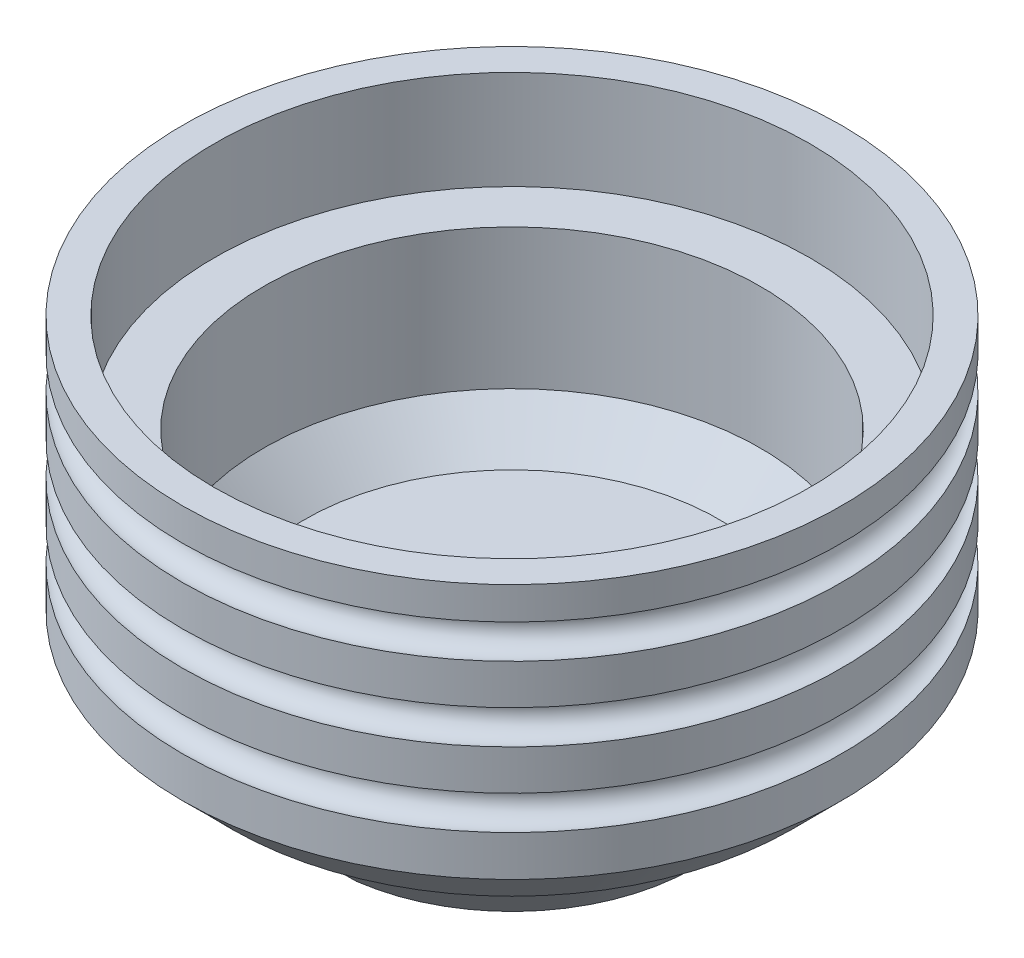
SolidWorks part; units mm, degrees
material "ABS PC"
ref_plane "正面" through (0, 0, 0) normal (0, 0, 1) x (1, 0, 0)
ref_plane "平面" through (0, 0, 0) normal (0, 1, 0) x (1, 0, 0)
ref_plane "右側面" through (0, 0, 0) normal (1, 0, 0) x (0, 0, -1)
sketch "ｽｹｯﾁ2" plane through (0, 0, 0) normal (1, 0, 0) x (0, 0, -1)
  line L0 (4, -2) -> (4, -27.3) construction
  line L1 (-1.125, -19) -> (-1.125, -6)
  line L2 (-1.125, -6) -> (-26.15, -6)
  line L3 (-26.15, -6) -> (-26.15, 16)
  line L4 (-26.15, 16) -> (-32.15, 16)
  line L5 (-32.15, 16) -> (-32.15, 28)
  line L6 (-32.15, 28) -> (-36, 28)
  line L7 (-36, 28) -> (-36, -9)
  line L14 (-36, -9) -> (-16.125, -9)
  line L16 (-1, -2) -> (9, -2) construction
  line L17 (-9.15, -3) -> (17.15, -3) construction
  line L19 (-1.125, -19) -> (-16.125, -19)
  line L20 (-16.125, -19) -> (-16.125, -9)
  line L21 (-35.5, 13) -> (-26.15, 13) construction
  line L22 (-35.5, 28) -> (-35.5, -9) construction
  circle A0 centre (-35.5, 22) radius 2.125
  circle A2 centre (-35.5, 13) radius 2.125
  circle A3 centre (-35.5, 4) radius 2.125
  point P15 (0, 0)
  dimension "D11" = 4.25
  dimension "D1" = 10.25
  dimension "D2" = 37
  dimension "D3" = 15
  dimension "D4" = 3
  dimension "D5" = 80
  dimension "D6" = 72.3
  dimension "D7" = 6
  dimension "D8" = 12
  dimension "2" = 3
  dimension "D9" = 10
  dimension "D10" = 15
  dimension "D12" = 0.5
  dimension "D13" = 9
revolve "回転1" add sketch "ｽｹｯﾁ2" angle 360 about L0 region at (0, -18.4147, 8.625)
chamfer "面取り1" distance 5 angle 45 1 edges at (0, -6, 26.15)
sketch "ｽｹｯﾁ3" plane through (0, -19, 0) normal (0, -1, 0) x (1, 0, 0)
  line L1 (-3.075, 0.1) -> (3.075, 0.1)
  line L2 (-3, 0) -> (3, 0) construction
  circle A1 centre (0, -4) radius 5.125 construction
  circle A2 centre (0, -4) radius 5.125
  dimension "D1" = 0.1
extrude "ﾎﾞｽ - 押し出し1" add sketch "ｽｹｯﾁ3" against normal blind 11.5 contours L1 region at (0, -19, 0.5137)
chamfer "面取り2" distance 12 angle 45 1 edges at (0, -9, 16.125)
sketch "ｽｹｯﾁ4" plane through (0, 0, 0.1) normal (0, 0, -1) x (-1, 0, 0)
  line L0 (0, -18.5) -> (0, -15.5002) construction
  line L2 (-3, -14.0001) -> (3, -14.0001)
  line L3 (-3, -14.0001) -> (-3, -20.0001)
  line L4 (-3, -20.0001) -> (3, -20.0001)
  line L5 (3, -14.0001) -> (3, -20.0001)
  line L6 (-3, -14.0001) -> (3, -20.0001) construction
  line L7 (-3, -20.0001) -> (3, -14.0001) construction
  spline S0 degree 3 poles (0, -18.5) (0.1532, -18.5) (0.3083, -18.4759) (0.4538, -18.4297) (0.6168, -18.378) (0.7722, -18.2971) (0.9074, -18.1944) (1.0388, -18.0946) (1.1548, -17.9715) (1.2466, -17.8343) (1.3352, -17.7019) (1.4036, -17.5529) (1.4462, -17.3983) (1.4893, -17.2418) (1.5069, -17.0752) (1.4975, -16.9127) (1.4876, -16.7431) (1.4478, -16.5729) (1.3822, -16.4173) (1.3163, -16.2609) (1.2224, -16.1145) (1.1087, -15.9897) (0.999, -15.8692) (0.8677, -15.7656) (0.7245, -15.6866) (0.5846, -15.6094) (0.4296, -15.5539) (0.2714, -15.5248) (0.1096, -15.495) (-0.06, -15.4922) (-0.2228, -15.5166) (-0.3916, -15.542) (-0.558, -15.5974) (-0.7075, -15.6773) (-0.8561, -15.7568) (-0.9924, -15.8627) (-1.1058, -15.9865) (-1.2147, -16.1053) (-1.3055, -16.2437) (-1.3711, -16.3917) (-1.4359, -16.5377) (-1.4778, -16.697) (-1.4932, -16.857) (-1.5091, -17.0229) (-1.4966, -17.1942) (-1.4572, -17.3558) (-1.4166, -17.5221) (-1.3463, -17.6829) (-1.2529, -17.8248) (-1.1614, -17.9637) (-1.0454, -18.0884) (-0.9137, -18.1896) (-0.7853, -18.2882) (-0.6385, -18.3671) (-0.4843, -18.4197) (-0.3299, -18.4723) (-0.1638, -18.5) (0, -18.5) (0.1532, -18.5) (0.3083, -18.4759) knots -0.0521 0 0 0 0.048635 0.048635 0.048635 0.10323 0.10323 0.10323 0.156231 0.156231 0.156231 0.207339 0.207339 0.207339 0.259122 0.259122 0.259122 0.313213 0.313213 0.313213 0.367545 0.367545 0.367545 0.419925 0.419925 0.419925 0.471108 0.471108 0.471108 0.523516 0.523516 0.523516 0.577917 0.577917 0.577917 0.631926 0.631926 0.631926 0.683723 0.683723 0.683723 0.734821 0.734821 0.734821 0.787892 0.787892 0.787892 0.842513 0.842513 0.842513 0.89589 0.89589 0.89589 0.9479 0.9479 0.9479 1 1 1 1.048635 1.048635 1.048635 only from (0, -18.5) to (0, -18.5) construction
  spline S1 degree 3 poles (0, -18.5) (0.1532, -18.5) (0.3083, -18.4759) (0.4538, -18.4297) (0.6168, -18.378) (0.7722, -18.2971) (0.9074, -18.1944) (1.0388, -18.0946) (1.1548, -17.9715) (1.2466, -17.8343) (1.3352, -17.7019) (1.4036, -17.5529) (1.4462, -17.3983) (1.4893, -17.2418) (1.5069, -17.0752) (1.4975, -16.9127) (1.4876, -16.7431) (1.4478, -16.5729) (1.3822, -16.4173) (1.3163, -16.2609) (1.2224, -16.1145) (1.1087, -15.9897) (0.999, -15.8692) (0.8677, -15.7656) (0.7245, -15.6866) (0.5846, -15.6094) (0.4296, -15.5539) (0.2714, -15.5248) (0.1096, -15.495) (-0.06, -15.4922) (-0.2228, -15.5166) (-0.3916, -15.542) (-0.558, -15.5974) (-0.7075, -15.6773) (-0.8561, -15.7568) (-0.9924, -15.8627) (-1.1058, -15.9865) (-1.2147, -16.1053) (-1.3055, -16.2437) (-1.3711, -16.3917) (-1.4359, -16.5377) (-1.4778, -16.697) (-1.4932, -16.857) (-1.5091, -17.0229) (-1.4966, -17.1942) (-1.4572, -17.3558) (-1.4166, -17.5221) (-1.3463, -17.6829) (-1.2529, -17.8248) (-1.1614, -17.9637) (-1.0454, -18.0884) (-0.9137, -18.1896) (-0.7853, -18.2882) (-0.6385, -18.3671) (-0.4843, -18.4197) (-0.3299, -18.4723) (-0.1638, -18.5) (0, -18.5) (0.1532, -18.5) (0.3083, -18.4759) knots -0.0521 0 0 0 0.048635 0.048635 0.048635 0.10323 0.10323 0.10323 0.156231 0.156231 0.156231 0.207339 0.207339 0.207339 0.259122 0.259122 0.259122 0.313213 0.313213 0.313213 0.367545 0.367545 0.367545 0.419925 0.419925 0.419925 0.471108 0.471108 0.471108 0.523516 0.523516 0.523516 0.577917 0.577917 0.577917 0.631926 0.631926 0.631926 0.683723 0.683723 0.683723 0.734821 0.734821 0.734821 0.787892 0.787892 0.787892 0.842513 0.842513 0.842513 0.89589 0.89589 0.89589 0.9479 0.9479 0.9479 1 1 1 1.048635 1.048635 1.048635 only from (0, -18.5) to (0, -18.5) construction
  point P1 (0, -17.0001)
  point P8 (0, 0)
  point P9 (0, 0)
  point P10 (0, 0)
  dimension "D1" = 6
  dimension "D2" = 6
extrude "ｶｯﾄ - 押し出し1" cut sketch "ｽｹｯﾁ4" against normal through all from offset 16 offset against normal yes
extrude "ｶｯﾄ - 押し出し2" cut sketch "ｽｹｯﾁ4<2>" along normal through all from offset 25
sketch "ｽｹｯﾁ4<2>" plane through (0, 0, 0.1) normal (0, 0, -1) x (-1, 0, 0) same geometry as "ｽｹｯﾁ4"
sketch "ｽｹｯﾁ5" plane through (0, 0, 16.1) normal (0, 0, 1) x (1, 0, 0)
  line L0 (0, -14.0001) -> (0, -17.0001) construction
  line L1 (-3, -14.0001) -> (3, -14.0001) construction
  circle A0 centre (0, -17.0001) radius 1.65
  dimension "D2" = 3.3
  dimension "D1" = 3
extrude "ｶｯﾄ - 押し出し3" cut sketch "ｽｹｯﾁ5" against normal through all
chamfer "面取り3" distance 6 angle 45 1 edges at (0, -9, 36)
